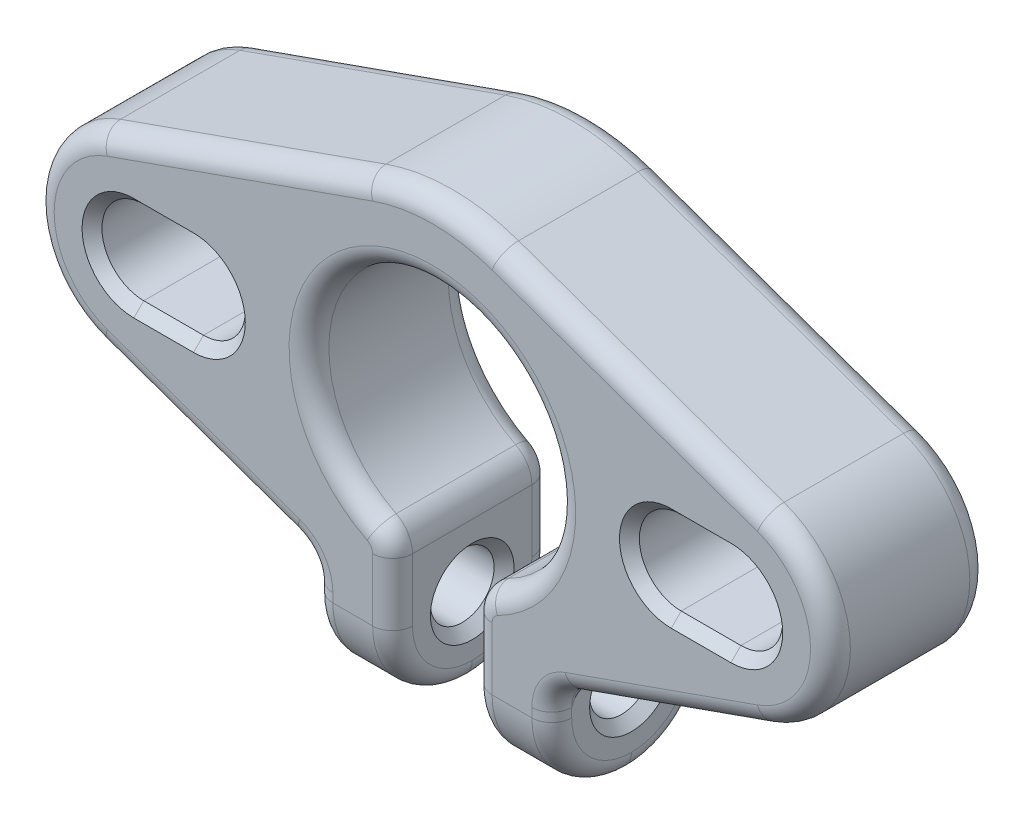
SolidWorks part; units mm, degrees
ref_plane "Спереди" through (0, 0, 0) normal (0, 0, 1) x (1, 0, 0)
ref_plane "Сверху" through (0, 0, 0) normal (0, 1, 0) x (1, 0, 0)
ref_plane "Справа" through (0, 0, 0) normal (1, 0, 0) x (0, 0, -1)
sketch "Эскиз1" plane through (0, 0, 0) normal (0, 0, 1) x (1, 0, 0)
  line L0 (-32.3801, 0) -> (35.5563, 0) construction
  line L1 (-15, 2.1) -> (-12, 2.1)
  line L2 (-15, -2.1) -> (-12, -2.1)
  line L3 (12, 2.1) -> (15, 2.1)
  line L4 (12, -2.1) -> (15, -2.1)
  line L5 (-3.3333, 9.4281) -> (-16.6667, 4.714)
  line L6 (3.3333, 9.4281) -> (16.6667, 4.714)
  line L7 (0, 14.3867) -> (0, -20.9882) construction
  line L8 (-2, -5.8686) -> (-2, -14)
  line L9 (2, -5.8686) -> (2, -14)
  line L10 (-6, -14) -> (-2, -14)
  line L11 (6, -14) -> (6, -8.4853)
  line L12 (-6, -14) -> (-6, -8.4853)
  line L13 (16.6667, -4.714) -> (6, -8.4853)
  line L14 (-16.6667, -4.714) -> (-6, -8.4853)
  line L15 (2, -14) -> (6, -14)
  arc A0 (2, -5.8686) -> (-2, -5.8686) centre (0, 0) ccw
  arc A1 (-15, 2.1) -> (-15, -2.1) centre (-15, 0) ccw
  arc A2 (15, -2.1) -> (15, 2.1) centre (15, 0) ccw
  arc A3 (-12, -2.1) -> (-12, 2.1) centre (-12, 0) ccw
  arc A4 (12, 2.1) -> (12, -2.1) centre (12, 0) ccw
  arc A5 (-16.6667, 4.714) -> (-16.6667, -4.714) centre (-15, 0) ccw
  arc A6 (16.6667, -4.714) -> (16.6667, 4.714) centre (15, 0) ccw
  arc A8 (3.3333, 9.4281) -> (-3.3333, 9.4281) centre (0, 0) ccw
  dimension "D1" = 12.4
  dimension "D2" = 4.2
  dimension "D7" = 10
  dimension "D3" = 15
  dimension "D4" = 15
  dimension "D5" = 3
  dimension "D6" = 3
  dimension "D9" = 2
  dimension "D10" = 2
  dimension "D11" = 14
  dimension "D12" = 4
  dimension "D13" = 4
extrude "Бобышка-Вытянуть1" add sketch "Эскиз1" along normal blind 8
fillet "Скругление4" radius 1.5 4 edges at (6, -8.4853, 4) (-6, -8.4853, 4) (-2, -5.8686, 4) (2, -5.8686, 4)
sketch "Эскиз2" plane through (6, 0, 0) normal (1, 0, 0) x (0, 0, -1)
  line L0 (-8, -14) -> (0, -14) construction
  line L1 (-4, -14) -> (-4, -8.7504) construction
  line L2 (-13.2293, -10) -> (5.0836, -10) construction
  line L4 (-0.8246, -10) -> (-2.4123, -7.25)
  line L5 (-2.4123, -7.25) -> (-5.5877, -7.25)
  line L6 (-5.5877, -7.25) -> (-7.1754, -10)
  line L7 (-7.1754, -10) -> (-5.5877, -12.75)
  line L8 (-5.5877, -12.75) -> (-2.4123, -12.75)
  line L9 (-2.4123, -12.75) -> (-0.8246, -10)
  circle A0 centre (-4, -10) radius 1.6
  circle A1 centre (-4, -10) radius 2.75 construction
  circle A2 centre (-4, -10) radius 3
  point P0 (-4, -14)
  point P6 (-4, -10)
  dimension "D2" = 3.2
  dimension "D3" = 6
  dimension "D1" = 4
extrude "Вырез-Вытянуть1" cut sketch "Эскиз2" against normal through all from offset 10 contours A0
extrude "Вырез-Вытянуть2" cut sketch "Эскиз2<3>" along normal through all contours A2
sketch "Эскиз2<3>" plane through (6, 0, 0) normal (1, 0, 0) x (0, 0, -1) same geometry as "Эскиз2"
extrude "Вырез-Вытянуть3" cut sketch "Эскиз2<4>" against normal through all from offset 12 contours L7 L8 L9 L4 L5 L6 offset against normal yes
sketch "Эскиз2<4>" plane through (6, 0, 0) normal (1, 0, 0) x (0, 0, -1) same geometry as "Эскиз2"
fillet "Скругление1" radius 4 4 edges at (4, -14, 8) (4, -14, 0) (-4, -14, 0) (-4, -14, 8)
fillet "Скругление2" radius 1 40 edges at (-2, -8.4293, 8) (-2, -8.4293, 0) (-2, -12.8284, 1.1716) (2, -8.4293, 0) (2, -12.8284, 1.1716) (2, -8.4293, 8) (11.8333, -6.4229, 0) (20, 0, 0) (10, 7.0711, 0) (0, 10, 0) (-10, 7.0711, 0) (-20, 0, 0) (6, -9.773, 8) (6, -9.773, 0) (6, -12.8284, 1.1716) (-6, -9.773, 0) (-6, -12.8284, 1.1716) (-6, -9.773, 8) (11.8333, -6.4229, 8) (20, 0, 8) (10, 7.0711, 8) (0, 10, 8) (-10, 7.0711, 8) (-20, 0, 8) (-2, -12.8284, 6.8284) (2, -12.8284, 6.8284) (-11.8333, -6.4229, 0) (6, -12.8284, 6.8284) (-6, -12.8284, 6.8284) (-11.8333, -6.4229, 8) (6.2753, -8.6799, 0) (6.2753, -8.6799, 8) (-6.2753, -8.6799, 0) (-6.2753, -8.6799, 8) (2.2208, -6.0752, 0) (0, 6.2, 0) (-2.2208, -6.0752, 0) (-2.2208, -6.0752, 8) (0, 6.2, 8) (2.2208, -6.0752, 8)
chamfer "Фаска1" distance 0.5 angle 45 20 edges at (-6, -10, 2.4) (2, -8.4, 4) (6, -10, 5.6) (-2, -11.6, 4) (13.5, 2.1, 8) (9.9, 0, 8) (17.1, 0, 8) (13.5, -2.1, 8) (13.5, 2.1, 0) (9.9, 0, 0) (17.1, 0, 0) (13.5, -2.1, 0) (-13.5, 2.1, 0) (-17.1, 0, 0) (-9.9, 0, 0) (-13.5, -2.1, 0) (-13.5, 2.1, 8) (-17.1, 0, 8) (-9.9, 0, 8) (-13.5, -2.1, 8)
